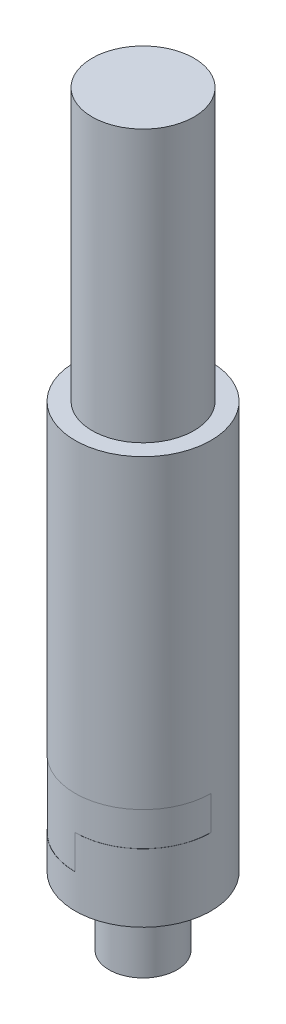
SolidWorks part; units mm, degrees
ref_plane "Front Plane" through (0, 0, 0) normal (0, 0, 1) x (1, 0, 0)
ref_plane "Top Plane" through (0, 0, 0) normal (0, 1, 0) x (1, 0, 0)
ref_plane "Right Plane" through (0, 0, 0) normal (1, 0, 0) x (0, 0, -1)
sketch "Sketch1" plane through (0, 0, 0) normal (0, 1, 0) x (1, 0, 0)
  circle A0 centre (0, 0) radius 9.525
  dimension "D1" = 19.05
extrude "Boss-Extrude1" add sketch "Sketch1" along normal blind 50.8
sketch "Sketch2" plane through (0, 0, 0) normal (0, -1, 0) x (1, 0, 0)
  circle A0 centre (0, 0) radius 12.7
  dimension "D1" = 25.4
extrude "Boss-Extrude2" add sketch "Sketch2" along normal blind 76.2
sketch "Sketch3" plane through (0, -76.2, 0) normal (0, -1, 0) x (1, 0, 0)
  circle A0 centre (0, 0) radius 6.35
  dimension "D1" = 12.7
extrude "Boss-Extrude3" add sketch "Sketch3" along normal blind 12.7
ref_plane "Plane1" through (0, -69.85, 0) normal (0, -1, 0) x (-1, 0, 0)
sketch "Sketch4" plane through (0, -69.85, 0) normal (0, -1, 0) x (-1, 0, 0)
  line L0 (0, 12.7) -> (0, 12.6746)
  line L1 (0, -12.6746) -> (0, -12.7)
  arc A0 (0, -12.7) -> (0, 12.7) centre (0, 0) ccw
  arc A1 (0, -12.6746) -> (0, 12.6746) centre (0, 0) ccw
  circle A2 centre (0, 0) radius 12.7 construction
  dimension "D1" = 0.0254
extrude "Cut-Extrude1" cut sketch "Sketch4" against normal blind 6.35
sketch "Sketch5" plane through (0, -63.5, 0) normal (0, -1, 0) x (1, 0, 0)
  line L0 (-12.7, 0) -> (-12.6746, 0)
  line L1 (12.6746, 0) -> (12.7, 0)
  arc A0 (12.7, 0) -> (-12.7, 0) centre (0, 0) ccw
  circle A1 centre (0, 0) radius 12.7 construction
  arc A2 (12.6746, 0) -> (-12.6746, 0) centre (0, 0) ccw
  dimension "D1" = 0.0254
extrude "Cut-Extrude2" cut sketch "Sketch5" against normal blind 6.35
